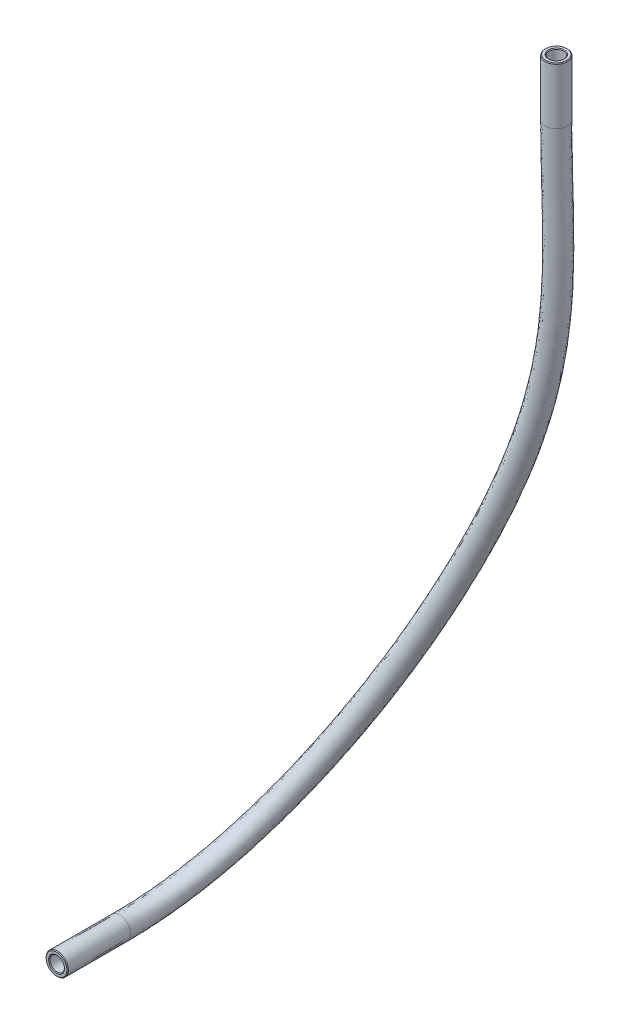
SolidWorks part; units mm, degrees
ref_plane "Front Plane" through (0, 0, 0) normal (0, 0, 1) x (1, 0, 0)
ref_plane "Top Plane" through (0, 0, 0) normal (0, 1, 0) x (1, 0, 0)
ref_plane "Right Plane" through (0, 0, 0) normal (1, 0, 0) x (0, 0, -1)
sketch "Sketch1" plane through (0, -117.5823, 0) normal (0, -1, 0) x (1, 0, 0)
  circle A0 centre (-150.0853, 9.525) radius 1.3
  circle A1 centre (-150.0853, 9.525) radius 2
  circle A2 centre (-150.0853, 9.525) radius 3.6 construction
  dimension "D1" = 2.6
  dimension "D2" = 4
sketch3d "3DSketch1"
  line L0 (-188.7379, -245.2343, 61.0875) -> (-188.7379, -245.2343, 49.6875)
  line L1 (-150.0853, -119.6823, 9.525) -> (-150.0853, -109.4823, 9.525)
  spline S0 degree 3 poles (-188.7379, -245.2343, 49.6875) (-188.7379, -245.2343, 20.826) (-147.1626, -170.6811, 6.4074) (-150.0853, -139.951, 9.525) (-150.0853, -119.6823, 9.525) knots 0 0 0 0 0.537487 1 1 1 1
sweep "Sweep1" add profiles "Sketch1" path "3DSketch1"
chamfer "Chamfer1" distance 0.127 angle 45 4 edges at (-190.1073, -246.6919, 61.0875) (-189.628, -246.1817, 61.0875) (-150.0853, -109.4823, 7.525) (-150.0853, -109.4823, 8.225)
